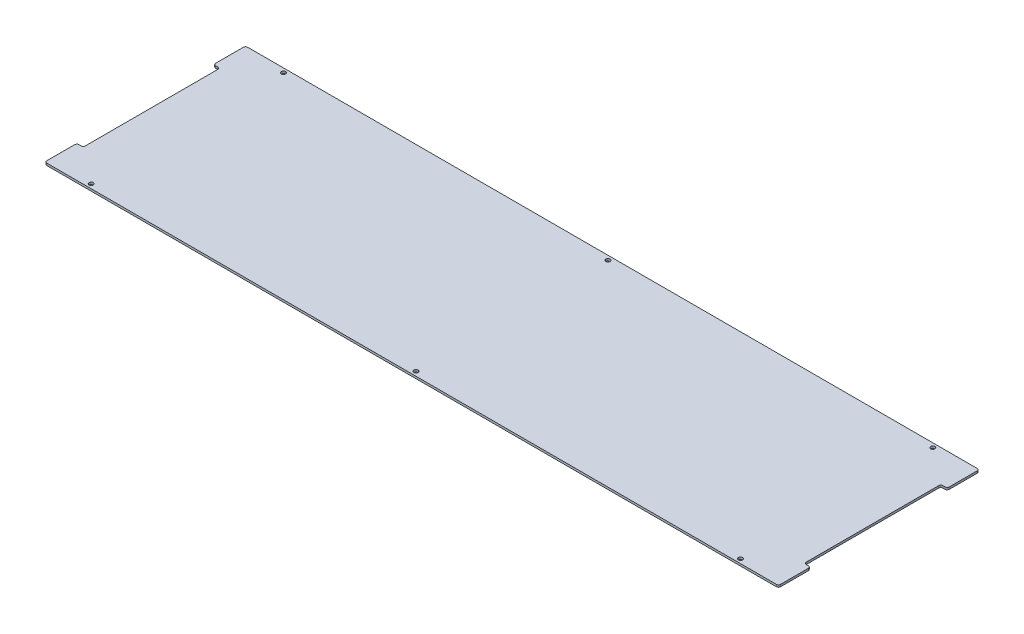
SolidWorks part; units mm, degrees
ref_plane "Front Plane" through (0, 0, 0) normal (0, 0, 1) x (1, 0, 0)
ref_plane "Top Plane" through (0, 0, 0) normal (0, 1, 0) x (1, 0, 0)
ref_plane "Right Plane" through (0, 0, 0) normal (1, 0, 0) x (0, 0, -1)
sketch "Sketch1" plane through (0, 0, 0) normal (0, 1, 0) x (1, 0, 0)
  line L1 (-545.3062, -149.225) -> (545.3062, -149.225)
  line L2 (-545.3062, -149.225) -> (-545.3062, 149.225)
  line L3 (-545.3062, 149.225) -> (545.3062, 149.225)
  line L4 (545.3062, -149.225) -> (545.3062, 149.225)
  line L5 (-545.3062, -149.225) -> (545.3062, 149.225) construction
  line L6 (-545.3062, 149.225) -> (545.3062, -149.225) construction
  point P0 (0, 0)
  dimension "D1" = 1090.6125
  dimension "D2" = 298.45
extrude "Boss-Extrude1" add sketch "Sketch1" along normal blind 3.175
sketch "Sketch2" plane through (0, 3.175, 0) normal (0, 1, 0) x (1, 0, 0)
  line L0 (545.3062, -149.225) -> (545.3062, 149.225) construction
  line L1 (545.3062, 101.6) -> (535.7812, 101.6)
  line L2 (545.3062, 101.6) -> (545.3062, -101.6)
  line L3 (545.3062, -101.6) -> (535.7812, -101.6)
  line L4 (535.7812, 101.6) -> (535.7812, -101.6)
  point P6 (535.7812, 0)
  dimension "D1" = 203.2
  dimension "D2" = 9.525
extrude "Cut-Extrude1" cut sketch "Sketch2" against normal through all
fillet "Fillet1" radius 3.175 2 edges at (535.7812, 1.5875, 101.6) (535.7812, 1.5875, -101.6)
mirror "Mirror1" about plane through (0, 0, 0) normal (1, 0, 0) of "Cut-Extrude1", "Fillet1"
hole_wizard "1/4 (0.25) Diameter Hole1" positions "Sketch3" profile "Sketch4" hole size "1/4" standard "ANSI Inch" end condition through all
sketch "Sketch3" plane through (0, 3.175, 0) normal (0, 1, 0) x (1, 0, 0)
  line L1 (545.3062, 149.225) -> (-545.3062, 149.225) construction
  point P0 (482.6, 142.875)
  point P2 (0, 142.875)
  point P4 (-482.6, 142.875)
  dimension "D1" = 482.6
  dimension "D3" = 965.2
  dimension "D4" = 6.35
sketch "Sketch4" plane through (482.6, 3.175, -142.875) normal (1, 0, 0) x (0, 0, 1)
  line L0 (0, 0) -> (0, 3.175)
  line L1 (0, 3.175) -> (3.175, 3.175)
  line L2 (3.175, 3.175) -> (3.175, 0)
  line L5 (3.175, 0) -> (0, 0)
  line L11 (0, -6.35) -> (0, 107.95) construction
  dimension "Thru Hole Dia." = 6.35
  dimension "Thru Hole Depth" = 3.175
mirror "Mirror2" about plane through (0, 0, 0) normal (0, 0, 1) of "1/4 (0.25) Diameter Hole1"
fillet "Fillet2" radius 3.175 8 edges at (-545.3062, 1.5875, 149.225) (-545.3062, 1.5875, 101.6) (-545.3062, 1.5875, -101.6) (-545.3062, 1.5875, -149.225) (545.3062, 1.5875, 149.225) (545.3062, 1.5875, 101.6) (545.3062, 1.5875, -101.6) (545.3062, 1.5875, -149.225)
